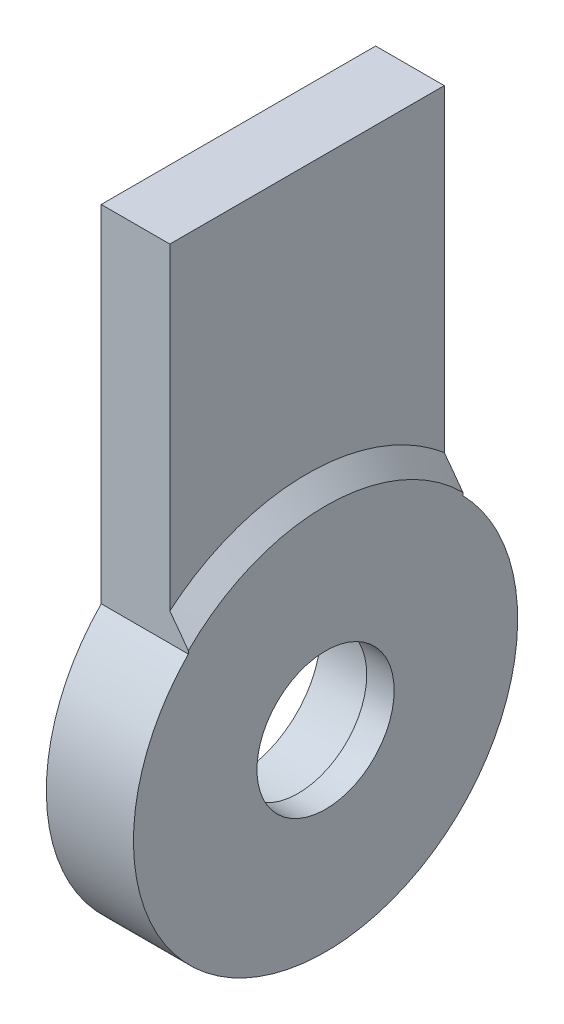
SolidWorks part; units mm, degrees
material "6061-T6 (SS)"
ref_plane "Front Plane" through (0, 0, 0) normal (0, 0, 1) x (1, 0, 0)
ref_plane "Top Plane" through (0, 0, 0) normal (0, 1, 0) x (1, 0, 0)
ref_plane "Right Plane" through (0, 0, 0) normal (1, 0, 0) x (0, 0, -1)
sketch "Sketch1" plane through (0, 0, 0) normal (1, 0, 0) x (0, 0, -1)
  line L3 (0, 0) -> (0, 37.3) construction
  line L11 (-10, 35) -> (10, 35)
  line L12 (-10, 35) -> (-10, 9.798)
  line L13 (10, 35) -> (10, 9.798)
  arc A1 (-10, 9.798) -> (10, 9.798) centre (0, 0) ccw construction
  arc A4 (-10, 9.798) -> (10, 9.798) centre (0, 0) ccw
  circle A6 centre (0, 0) radius 5
  point P3 (7.4406, 11.8591)
  point P5 (0, 0)
  dimension "D1" = 10
  dimension "D2" = 35
  dimension "D4" = 14
  dimension "D3" = 20
extrude "Boss-Extrude1" add sketch "Sketch1" along normal mid plane 6.35
sketch "Sketch2" plane through (-3.175, 0, 0) normal (-1, 0, 0) x (0, 0, 1)
  circle A0 centre (0, 0) radius 6
  dimension "D1" = 12
extrude "Cut-Extrude1" cut sketch "Sketch2" against normal offset from surface (4.35 mm away) 2 up to face at (3.175, 16.4495, 0)
sketch "Sketch4" plane through (3.175, 0, 0) normal (-1, 0, 0) x (0, 0, 1)
  line L0 (-16.065, 41.7777) -> (20.7511, 41.7777)
  line L3 (-19.8997, 37.4718) -> (-16.065, 41.7777)
  line L4 (-19.8997, 37.4718) -> (-15.1627, -1.5314)
  line L5 (-15.1627, -1.5314) -> (-13.967, 0.9602)
  line L6 (20.7511, 41.7777) -> (18.6845, 1.2845)
  line L7 (18.6845, 1.2845) -> (13.967, 0.9602)
  arc A1 (13.967, 0.9602) -> (-13.967, 0.9602) centre (0, 0) ccw
  arc A2 (-10, 9.798) -> (10, 9.798) centre (0, 0) ccw construction
extrude "Cut-Extrude2" cut sketch "Sketch4" along normal offset from surface (1.35 mm away) 5 up to face at (-3.175, 0, 6)
sketch "Sketch6" plane through (0, 35, 0) normal (0, 1, 0) x (1, 0, 0)
  line L0 (-3.175, 10) -> (-3.175, -10) construction
  line L5 (1.825, 10) -> (-3.175, 10) construction
  line L9 (12.7, -10) -> (-3.175, -10)
  line L10 (12.7, -10) -> (12.7, 10)
  line L11 (12.7, 10) -> (-3.175, 10)
  line L12 (-3.175, -10) -> (-3.175, 10)
  line L13 (12.7, -10) -> (-3.175, 10) construction
  line L14 (12.7, 10) -> (-3.175, -10) construction
  line L15 (4.7625, 10) -> (4.7625, -10) construction
  line L16 (-45.7658, 0) -> (12.7, 0) construction
  circle A2 centre (4.7625, -5) radius 2
  circle A3 centre (4.7625, 5) radius 2
  point P16 (4.7625, 0)
  dimension "D5" = 4
  dimension "D4" = 15.875
  dimension "D6" = 5
extrude "Boss-Extrude3" [suppressed] add sketch "Sketch6" along normal blind 3.175
sketch "Sketch7" [suppressed] plane through (1.825, 0, 0) normal (1, 0, 0) x (0, 0, -1)
  line L0 (0, 32) -> (0, 14) construction
  line L1 (10, 32) -> (-10, 32) construction
  line L3 (-1.5875, 9.0567) -> (1.5875, 9.0567)
  line L4 (-1.5875, 9.0567) -> (-1.5875, 36.9433)
  line L5 (-1.5875, 36.9433) -> (1.5875, 36.9433)
  line L6 (1.5875, 9.0567) -> (1.5875, 36.9433)
  line L7 (-1.5875, 9.0567) -> (1.5875, 36.9433) construction
  line L8 (-1.5875, 36.9433) -> (1.5875, 9.0567) construction
  arc A0 (10, 9.798) -> (-10, 9.798) centre (0, 0) ccw construction
  point P7 (0, 23)
  dimension "D1" = 3.175
extrude "Boss-Extrude4" [suppressed] add sketch "Sketch7" along normal up to surface (2.35 mm away)
chamfer "Chamfer2" distance 1.5 angle 45 1 edges at (1.825, 14, 0)
sketch "Sketch8" plane through (-3.175, 0, 0) normal (-1, 0, 0) x (0, 0, 1)
  circle A0 centre (0, 0) radius 7.5
  circle A1 centre (0, 0) radius 12
  dimension "D1" = 24
  dimension "D2" = 15
extrude "Cut-Extrude3" cut sketch "Sketch8" against normal blind 0.75
